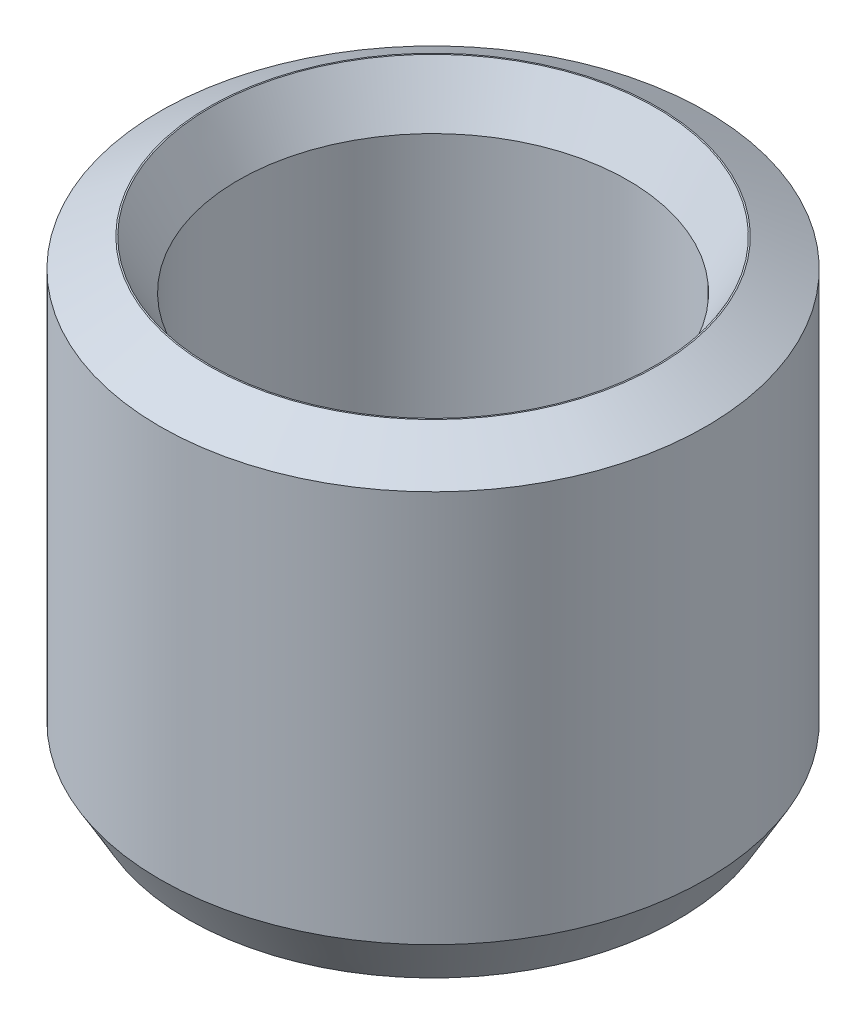
SolidWorks part; units mm, degrees
ref_plane "Front Plane" through (0, 0, 0) normal (0, 0, 1) x (1, 0, 0)
ref_plane "Top Plane" through (0, 0, 0) normal (0, 1, 0) x (1, 0, 0)
ref_plane "Right Plane" through (0, 0, 0) normal (1, 0, 0) x (0, 0, -1)
sketch "Sketch1" plane through (0, 0, 0) normal (0, 1, 0) x (1, 0, 0)
  circle A0 centre (0, 0) radius 10
  dimension "SLEEVE_OD" = 20
extrude "Boss-Extrude1" add sketch "Sketch1" along normal blind 17.1784
sketch "Sketch2" plane through (0, 0, 0) normal (0, 1, 0) x (1, 0, 0)
  circle A0 centre (0, 0) radius 7.1356
  dimension "BORE_D" = 14.2711
extrude "Cut-Extrude1" cut sketch "Sketch2" along normal through all
chamfer "Chamfer1" distance 1.0301 angle 60 4 edges at (0, 17.1784, 7.1356) (0, 0, 7.1356) (0, 0, 10) (0, 17.1784, 10) first distance on face at (0, 17.1784, 7.1356) first distance on face at (0, 0, 7.1356) first distance on face at (0, 17.1784, 10)
